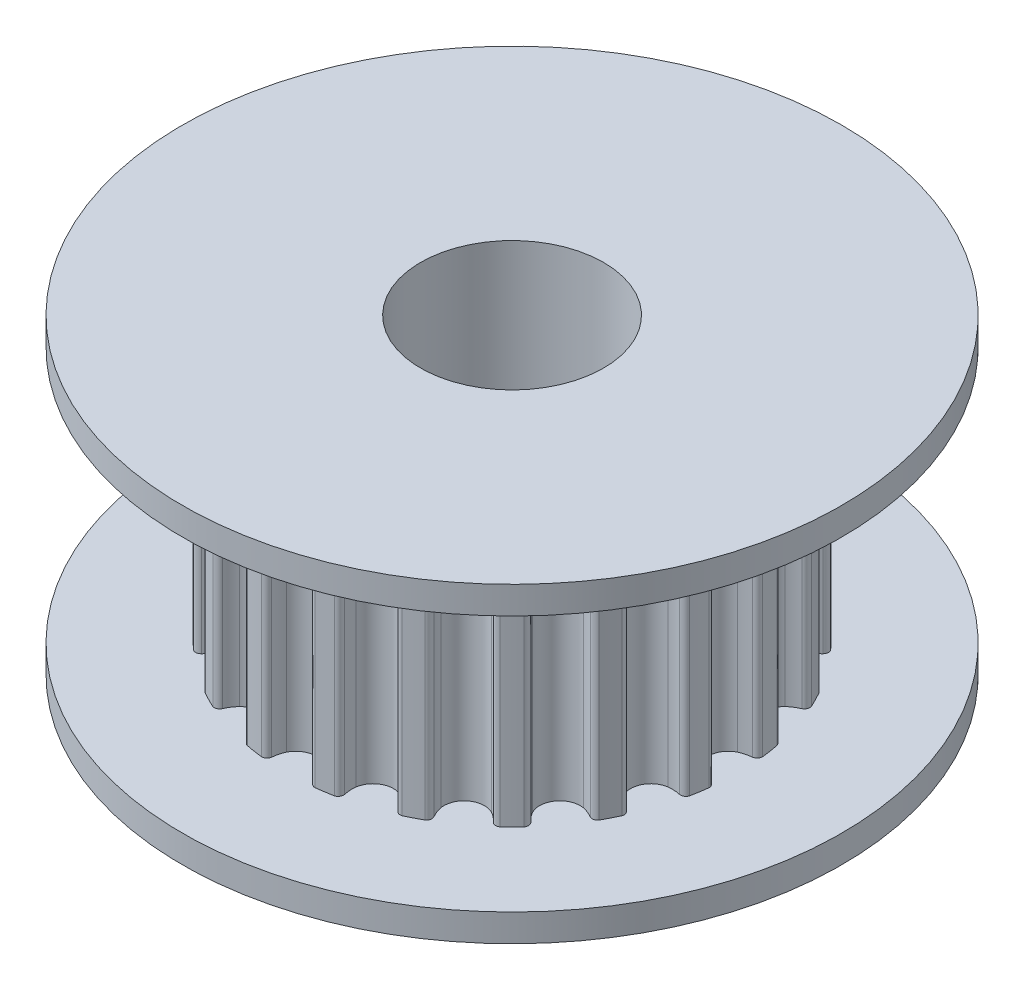
SolidWorks part; units mm, degrees
ref_plane "Front" through (0, 0, 0) normal (0, 0, 1) x (1, 0, 0)
ref_plane "Top" through (0, 0, 0) normal (0, 1, 0) x (1, 0, 0)
ref_plane "Right" through (0, 0, 0) normal (1, 0, 0) x (0, 0, -1)
sketch "Sketch1" plane through (0, 0, 0) normal (0, 0, 1) x (1, 0, 0)
  line L0 (0, 0) -> (0, 8.5) construction
  line L1 (2.5, 0) -> (2.5, 8.5)
  line L2 (2.5, 8.5) -> (9, 8.5)
  line L3 (9, 8.5) -> (9, 7.75)
  line L4 (9, 7.75) -> (6.3662, 7.75)
  line L5 (6.3662, 7.75) -> (6.3662, 0.75)
  line L6 (6.3662, 0.75) -> (9, 0.75)
  line L7 (9, 0.75) -> (9, 0)
  line L8 (9, 0) -> (2.5, 0)
  dimension "D1" = 8.5
  dimension "D2" = 7
  dimension "D3" = 18
  dimension "D4" = 12.7324
  dimension "D5" = 5
revolve "Revolve1" add sketch "Sketch1" angle 360 about L0
sketch "Sketch2" plane through (0, 0.75, 0) normal (0, 1, 0) x (1, 0, 0)
  circle A0 centre (0, 0) radius 6.3662 construction
  circle A1 centre (0, 0) radius 6.3662
  circle A3 centre (0, 0) radius 4.3662
  dimension "D1" = 2
extrude "Cut-Extrude1" cut sketch "Sketch2" along normal up to surface (7 mm away) up to face at (0, 7.75, -9)
sketch "Sketch3" plane through (0, 0.75, 0) normal (0, 1, 0) x (1, 0, 0)
  circle A0 centre (0, 0) radius 1.5
  arc A1 (6.1135, -0.7303) -> (5.9829, -0.5816) centre (5.9635, -0.7303) ccw
  arc A2 (5.659, -0.4964) -> (5.9829, -0.5816) centre (6.0717, 0.4144) ccw
  arc A3 (5.3522, 0) -> (5.659, -0.4964) centre (5.9072, 0) ccw
  arc A4 (5.659, 0.4964) -> (5.3522, 0) centre (5.9072, 0) ccw
  arc A5 (5.9829, 0.5816) -> (5.659, 0.4964) centre (6.0717, -0.4144) ccw
  arc A6 (5.9829, 0.5816) -> (6.1135, 0.7303) centre (5.9635, 0.7303) ccw
  arc A7 (6.1135, 0.7303) -> (6.0399, 1.1946) centre (0.0442, 0.007) ccw
  arc A8 (6.0399, 1.1946) -> (5.8698, 1.2957) centre (5.8973, 1.1482) ccw
  arc A9 (5.5354, 1.2766) -> (5.8698, 1.2957) centre (5.6465, 2.2704) ccw
  arc A10 (5.0902, 1.6539) -> (5.5354, 1.2766) centre (5.6181, 1.8254) ccw
  arc A11 (5.2286, 2.2208) -> (5.0902, 1.6539) centre (5.6181, 1.8254) ccw
  arc A12 (5.5103, 2.4019) -> (5.2286, 2.2208) centre (5.9026, 1.4821) ccw
  arc A13 (5.5103, 2.4019) -> (5.5886, 2.5838) centre (5.4459, 2.5374) ccw
  arc A14 (5.5886, 2.5838) -> (5.3752, 3.0025) centre (0.0399, 0.0203) ccw
  arc A15 (5.3752, 3.0025) -> (5.1821, 3.0461) centre (5.2538, 2.9144) ccw
  arc A16 (4.87, 2.9247) -> (5.1821, 3.0461) centre (4.6685, 3.9042) ccw
  arc A17 (4.33, 3.1459) -> (4.87, 2.9247) centre (4.779, 3.4722) ccw
  arc A18 (4.2864, 3.7279) -> (4.33, 3.1459) centre (4.779, 3.4722) ccw
  arc A19 (4.4984, 3.9872) -> (4.2864, 3.7279) centre (5.1557, 3.2336) ccw
  arc A20 (4.4984, 3.9872) -> (4.5166, 4.1843) centre (4.3953, 4.0961) ccw
  arc A21 (4.5166, 4.1843) -> (4.1843, 4.5166) centre (0.0317, 0.0317) ccw
  arc A22 (4.1843, 4.5166) -> (3.9872, 4.4984) centre (4.0961, 4.3953) ccw
  arc A23 (3.7279, 4.2864) -> (3.9872, 4.4984) centre (3.2336, 5.1557) ccw
  arc A24 (3.1459, 4.33) -> (3.7279, 4.2864) centre (3.4722, 4.779) ccw
  arc A25 (2.9247, 4.87) -> (3.1459, 4.33) centre (3.4722, 4.779) ccw
  arc A26 (3.0461, 5.1821) -> (2.9247, 4.87) centre (3.9042, 4.6685) ccw
  arc A27 (3.0461, 5.1821) -> (3.0025, 5.3752) centre (2.9144, 5.2538) ccw
  arc A28 (3.0025, 5.3752) -> (2.5838, 5.5886) centre (0.0203, 0.0399) ccw
  arc A29 (2.5838, 5.5886) -> (2.4019, 5.5103) centre (2.5374, 5.4459) ccw
  arc A30 (2.2208, 5.2286) -> (2.4019, 5.5103) centre (1.4821, 5.9026) ccw
  arc A31 (1.6539, 5.0902) -> (2.2208, 5.2286) centre (1.8254, 5.6181) ccw
  arc A32 (1.2766, 5.5354) -> (1.6539, 5.0902) centre (1.8254, 5.6181) ccw
  arc A33 (1.2957, 5.8698) -> (1.2766, 5.5354) centre (2.2704, 5.6465) ccw
  arc A34 (1.2957, 5.8698) -> (1.1946, 6.0399) centre (1.1482, 5.8973) ccw
  arc A35 (1.1946, 6.0399) -> (0.7303, 6.1135) centre (0.007, 0.0442) ccw
  arc A36 (0.7303, 6.1135) -> (0.5816, 5.9829) centre (0.7303, 5.9635) ccw
  arc A37 (0.4964, 5.659) -> (0.5816, 5.9829) centre (-0.4144, 6.0717) ccw
  arc A38 (0, 5.3522) -> (0.4964, 5.659) centre (0, 5.9072) ccw
  arc A39 (-0.4964, 5.659) -> (0, 5.3522) centre (0, 5.9072) ccw
  arc A40 (-0.5816, 5.9829) -> (-0.4964, 5.659) centre (0.4144, 6.0717) ccw
  arc A41 (-0.5816, 5.9829) -> (-0.7303, 6.1135) centre (-0.7303, 5.9635) ccw
  arc A42 (-0.7303, 6.1135) -> (-1.1946, 6.0399) centre (-0.007, 0.0442) ccw
  arc A43 (-1.1946, 6.0399) -> (-1.2957, 5.8698) centre (-1.1482, 5.8973) ccw
  arc A44 (-1.2766, 5.5354) -> (-1.2957, 5.8698) centre (-2.2704, 5.6465) ccw
  arc A45 (-1.6539, 5.0902) -> (-1.2766, 5.5354) centre (-1.8254, 5.6181) ccw
  arc A46 (-2.2208, 5.2286) -> (-1.6539, 5.0902) centre (-1.8254, 5.6181) ccw
  arc A47 (-2.4019, 5.5103) -> (-2.2208, 5.2286) centre (-1.4821, 5.9026) ccw
  arc A48 (-2.4019, 5.5103) -> (-2.5838, 5.5886) centre (-2.5374, 5.4459) ccw
  arc A49 (-2.5838, 5.5886) -> (-3.0025, 5.3752) centre (-0.0203, 0.0399) ccw
  arc A50 (-3.0025, 5.3752) -> (-3.0461, 5.1821) centre (-2.9144, 5.2538) ccw
  arc A51 (-2.9247, 4.87) -> (-3.0461, 5.1821) centre (-3.9042, 4.6685) ccw
  arc A52 (-3.1459, 4.33) -> (-2.9247, 4.87) centre (-3.4722, 4.779) ccw
  arc A53 (-3.7279, 4.2864) -> (-3.1459, 4.33) centre (-3.4722, 4.779) ccw
  arc A54 (-3.9872, 4.4984) -> (-3.7279, 4.2864) centre (-3.2336, 5.1557) ccw
  arc A55 (-3.9872, 4.4984) -> (-4.1843, 4.5166) centre (-4.0961, 4.3953) ccw
  arc A56 (-4.1843, 4.5166) -> (-4.5166, 4.1843) centre (-0.0317, 0.0317) ccw
  arc A57 (-4.5166, 4.1843) -> (-4.4984, 3.9872) centre (-4.3953, 4.0961) ccw
  arc A58 (-4.2864, 3.7279) -> (-4.4984, 3.9872) centre (-5.1557, 3.2336) ccw
  arc A59 (-4.33, 3.1459) -> (-4.2864, 3.7279) centre (-4.779, 3.4722) ccw
  arc A60 (-4.87, 2.9247) -> (-4.33, 3.1459) centre (-4.779, 3.4722) ccw
  arc A61 (-5.1821, 3.0461) -> (-4.87, 2.9247) centre (-4.6685, 3.9042) ccw
  arc A62 (-5.1821, 3.0461) -> (-5.3752, 3.0025) centre (-5.2538, 2.9144) ccw
  arc A63 (-5.3752, 3.0025) -> (-5.5886, 2.5838) centre (-0.0399, 0.0203) ccw
  arc A64 (-5.5886, 2.5838) -> (-5.5103, 2.4019) centre (-5.4459, 2.5374) ccw
  arc A65 (-5.2286, 2.2208) -> (-5.5103, 2.4019) centre (-5.9026, 1.4821) ccw
  arc A66 (-5.0902, 1.6539) -> (-5.2286, 2.2208) centre (-5.6181, 1.8254) ccw
  arc A67 (-5.5354, 1.2766) -> (-5.0902, 1.6539) centre (-5.6181, 1.8254) ccw
  arc A68 (-5.8698, 1.2957) -> (-5.5354, 1.2766) centre (-5.6465, 2.2704) ccw
  arc A69 (-5.8698, 1.2957) -> (-6.0399, 1.1946) centre (-5.8973, 1.1482) ccw
  arc A70 (-6.0399, 1.1946) -> (-6.1135, 0.7303) centre (-0.0442, 0.007) ccw
  arc A71 (-6.1135, 0.7303) -> (-5.9829, 0.5816) centre (-5.9635, 0.7303) ccw
  arc A72 (-5.659, 0.4964) -> (-5.9829, 0.5816) centre (-6.0717, -0.4144) ccw
  arc A73 (-5.3522, 0) -> (-5.659, 0.4964) centre (-5.9072, 0) ccw
  arc A74 (-5.659, -0.4964) -> (-5.3522, 0) centre (-5.9072, 0) ccw
  arc A75 (-5.9829, -0.5816) -> (-5.659, -0.4964) centre (-6.0717, 0.4144) ccw
  arc A76 (-5.9829, -0.5816) -> (-6.1135, -0.7303) centre (-5.9635, -0.7303) ccw
  arc A77 (-6.1135, -0.7303) -> (-6.0399, -1.1946) centre (-0.0442, -0.007) ccw
  arc A78 (-6.0399, -1.1946) -> (-5.8698, -1.2957) centre (-5.8973, -1.1482) ccw
  arc A79 (-5.5354, -1.2766) -> (-5.8698, -1.2957) centre (-5.6465, -2.2704) ccw
  arc A80 (-5.0902, -1.6539) -> (-5.5354, -1.2766) centre (-5.6181, -1.8254) ccw
  arc A81 (-5.2286, -2.2208) -> (-5.0902, -1.6539) centre (-5.6181, -1.8254) ccw
  arc A82 (-5.5103, -2.4019) -> (-5.2286, -2.2208) centre (-5.9026, -1.4821) ccw
  arc A83 (-5.5103, -2.4019) -> (-5.5886, -2.5838) centre (-5.4459, -2.5374) ccw
  arc A84 (-5.5886, -2.5838) -> (-5.3752, -3.0025) centre (-0.0399, -0.0203) ccw
  arc A85 (-5.3752, -3.0025) -> (-5.1821, -3.0461) centre (-5.2538, -2.9144) ccw
  arc A86 (-4.87, -2.9247) -> (-5.1821, -3.0461) centre (-4.6685, -3.9042) ccw
  arc A87 (-4.33, -3.1459) -> (-4.87, -2.9247) centre (-4.779, -3.4722) ccw
  arc A88 (-4.2864, -3.7279) -> (-4.33, -3.1459) centre (-4.779, -3.4722) ccw
  arc A89 (-4.4984, -3.9872) -> (-4.2864, -3.7279) centre (-5.1557, -3.2336) ccw
  arc A90 (-4.4984, -3.9872) -> (-4.5166, -4.1843) centre (-4.3953, -4.0961) ccw
  arc A91 (-4.5166, -4.1843) -> (-4.1843, -4.5166) centre (-0.0317, -0.0317) ccw
  arc A92 (-4.1843, -4.5166) -> (-3.9872, -4.4984) centre (-4.0961, -4.3953) ccw
  arc A93 (-3.7279, -4.2864) -> (-3.9872, -4.4984) centre (-3.2336, -5.1557) ccw
  arc A94 (-3.1459, -4.33) -> (-3.7279, -4.2864) centre (-3.4722, -4.779) ccw
  arc A95 (-2.9247, -4.87) -> (-3.1459, -4.33) centre (-3.4722, -4.779) ccw
  arc A96 (-3.0461, -5.1821) -> (-2.9247, -4.87) centre (-3.9042, -4.6685) ccw
  arc A97 (-3.0461, -5.1821) -> (-3.0025, -5.3752) centre (-2.9144, -5.2538) ccw
  arc A98 (-3.0025, -5.3752) -> (-2.5838, -5.5886) centre (-0.0203, -0.0399) ccw
  arc A99 (-2.5838, -5.5886) -> (-2.4019, -5.5103) centre (-2.5374, -5.4459) ccw
  arc A100 (-2.2208, -5.2286) -> (-2.4019, -5.5103) centre (-1.4821, -5.9026) ccw
  arc A101 (-1.6539, -5.0902) -> (-2.2208, -5.2286) centre (-1.8254, -5.6181) ccw
  arc A102 (-1.2766, -5.5354) -> (-1.6539, -5.0902) centre (-1.8254, -5.6181) ccw
  arc A103 (-1.2957, -5.8698) -> (-1.2766, -5.5354) centre (-2.2704, -5.6465) ccw
  arc A104 (-1.2957, -5.8698) -> (-1.1946, -6.0399) centre (-1.1482, -5.8973) ccw
  arc A105 (-1.1946, -6.0399) -> (-0.7303, -6.1135) centre (-0.007, -0.0442) ccw
  arc A106 (-0.7303, -6.1135) -> (-0.5816, -5.9829) centre (-0.7303, -5.9635) ccw
  arc A107 (-0.4964, -5.659) -> (-0.5816, -5.9829) centre (0.4144, -6.0717) ccw
  arc A108 (0, -5.3522) -> (-0.4964, -5.659) centre (0, -5.9072) ccw
  arc A109 (0.4964, -5.659) -> (0, -5.3522) centre (0, -5.9072) ccw
  arc A110 (0.5816, -5.9829) -> (0.4964, -5.659) centre (-0.4144, -6.0717) ccw
  arc A111 (0.5816, -5.9829) -> (0.7303, -6.1135) centre (0.7303, -5.9635) ccw
  arc A112 (0.7303, -6.1135) -> (1.1946, -6.0399) centre (0.007, -0.0442) ccw
  arc A113 (1.1946, -6.0399) -> (1.2957, -5.8698) centre (1.1482, -5.8973) ccw
  arc A114 (1.2766, -5.5354) -> (1.2957, -5.8698) centre (2.2704, -5.6465) ccw
  arc A115 (1.6539, -5.0902) -> (1.2766, -5.5354) centre (1.8254, -5.6181) ccw
  arc A116 (2.2208, -5.2286) -> (1.6539, -5.0902) centre (1.8254, -5.6181) ccw
  arc A117 (2.4019, -5.5103) -> (2.2208, -5.2286) centre (1.4821, -5.9026) ccw
  arc A118 (2.4019, -5.5103) -> (2.5838, -5.5886) centre (2.5374, -5.4459) ccw
  arc A119 (2.5838, -5.5886) -> (3.0025, -5.3752) centre (0.0203, -0.0399) ccw
  arc A120 (3.0025, -5.3752) -> (3.0461, -5.1821) centre (2.9144, -5.2538) ccw
  arc A121 (2.9247, -4.87) -> (3.0461, -5.1821) centre (3.9042, -4.6685) ccw
  arc A122 (3.1459, -4.33) -> (2.9247, -4.87) centre (3.4722, -4.779) ccw
  arc A123 (3.7279, -4.2864) -> (3.1459, -4.33) centre (3.4722, -4.779) ccw
  arc A124 (3.9872, -4.4984) -> (3.7279, -4.2864) centre (3.2336, -5.1557) ccw
  arc A125 (3.9872, -4.4984) -> (4.1843, -4.5166) centre (4.0961, -4.3953) ccw
  arc A126 (4.1843, -4.5166) -> (4.5166, -4.1843) centre (0.0317, -0.0317) ccw
  arc A127 (4.5166, -4.1843) -> (4.4984, -3.9872) centre (4.3953, -4.0961) ccw
  arc A128 (4.2864, -3.7279) -> (4.4984, -3.9872) centre (5.1557, -3.2336) ccw
  arc A129 (4.33, -3.1459) -> (4.2864, -3.7279) centre (4.779, -3.4722) ccw
  arc A130 (4.87, -2.9247) -> (4.33, -3.1459) centre (4.779, -3.4722) ccw
  arc A131 (5.1821, -3.0461) -> (4.87, -2.9247) centre (4.6685, -3.9042) ccw
  arc A132 (5.1821, -3.0461) -> (5.3752, -3.0025) centre (5.2538, -2.9144) ccw
  arc A133 (5.3752, -3.0025) -> (5.5886, -2.5838) centre (0.0399, -0.0203) ccw
  arc A134 (5.5886, -2.5838) -> (5.5103, -2.4019) centre (5.4459, -2.5374) ccw
  arc A135 (5.2286, -2.2208) -> (5.5103, -2.4019) centre (5.9026, -1.4821) ccw
  arc A136 (5.0902, -1.6539) -> (5.2286, -2.2208) centre (5.6181, -1.8254) ccw
  arc A137 (5.5354, -1.2766) -> (5.0902, -1.6539) centre (5.6181, -1.8254) ccw
  arc A138 (5.8698, -1.2957) -> (5.5354, -1.2766) centre (5.6465, -2.2704) ccw
  arc A139 (5.8698, -1.2957) -> (6.0399, -1.1946) centre (5.8973, -1.1482) ccw
  arc A140 (6.0399, -1.1946) -> (6.1135, -0.7303) centre (0.0442, -0.007) ccw
  circle A141 centre (0, 0) radius 4.3662 construction
  circle A142 centre (0, 0) radius 4.3662
extrude "Boss-Extrude1" add sketch "Sketch3" along normal up to surface (7 mm away) contours A139 A140 A1 A2 A3 A4 A5 A6 A7 A8 A9 A10 A11 A12 A13 A14 A15 A16 A17 A18 A19 A20 A21 A22 A23 A24 A25 A26 A27 A28 A29 A30 A31 A32 A33 A34 A35 A36 A37 A38 A39 A40 A41 A42 A43 A44 A45 A46 A47 A48 A49 region at (5.9104, 0.75, 0.9361) up to face at (0, 7.75, -9)
sketch "innermost_diameter" plane through (0, 7.75, 0) normal (0, -1, 0) x (1, 0, 0)
  circle A0 centre (0, 0) radius 5.3522
sketch "approx pitch diameter" plane through (0, 8.5, 0) normal (0, 1, 0) x (1, 0, 0)
  circle A0 centre (0, 0) radius 5.625
  dimension "D1" = 11.25
equation "\"D4@Sketch1\"=20*2/3.14159"
